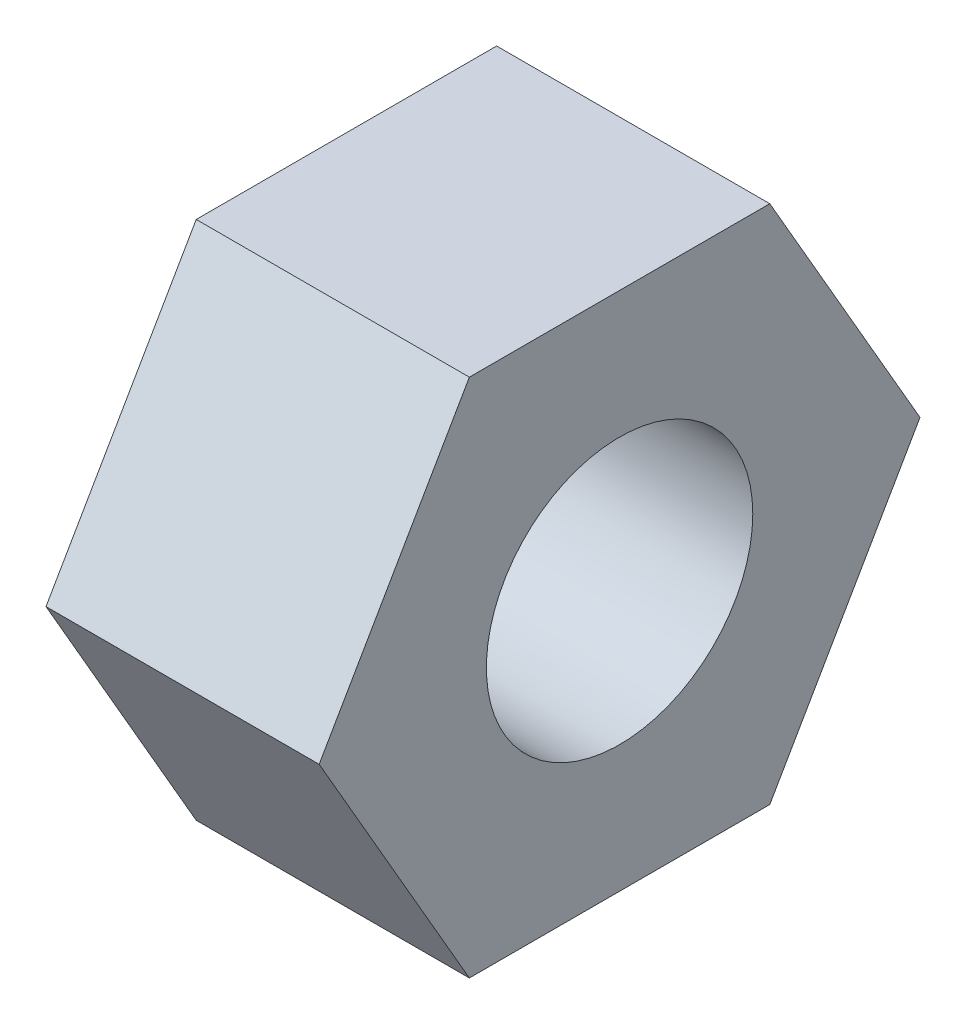
SolidWorks part; units mm, degrees
material "6061-T4 (SS)"
ref_plane "Front Plane" through (0, 0, 0) normal (0, 0, 1) x (1, 0, 0)
ref_plane "Top Plane" through (0, 0, 0) normal (0, 1, 0) x (1, 0, 0)
ref_plane "Right Plane" through (0, 0, 0) normal (1, 0, 0) x (0, 0, -1)
sketch "Sketch1" plane through (0, 0, 0) normal (1, 0, 0) x (0, 0, -1)
  line L0 (0, 0) -> (2.7496, 0) construction
  line L1 (2.7496, 0) -> (1.3748, 2.3812)
  line L2 (1.3748, 2.3812) -> (-1.3748, 2.3813)
  line L3 (-1.3748, 2.3813) -> (-2.7496, 0)
  line L4 (-2.7496, 0) -> (-1.3748, -2.3813)
  line L5 (-1.3748, -2.3813) -> (1.3748, -2.3813)
  line L6 (1.3748, -2.3813) -> (2.7496, 0)
  circle A0 centre (0, 0) radius 2.3812 construction
  point P1 (-2.0622, 1.1906)
  dimension "D1" = 4.7625
extrude "Boss-Extrude1" add sketch "Sketch1" along normal blind 2.5
sketch "Sketch2" plane through (2.5, 0, 0) normal (1, 0, 0) x (0, 0, -1)
  circle A0 centre (0, 0) radius 1.0922
  dimension "D1" = 2.1844
hole_wizard "#2 Clearance Hole1" positions "Sketch3" profile "Sketch4" hole size "#2" standard "ANSI Inch" end condition through all
sketch "Sketch3" plane through (2.5, 0, 0) normal (1, 0, 0) x (0, 0, -1)
  point P0 (0, 0)
sketch "Sketch4" plane through (2.5, 0, 0) normal (0, 1, 0) x (0, 0, -1)
  line L0 (0, 0) -> (0, 2.5)
  line L1 (0, 2.5) -> (1.2192, 2.5)
  line L2 (1.2192, 2.5) -> (1.2192, 0)
  line L5 (1.2192, 0) -> (0, 0)
  line L11 (0, -6.35) -> (0, 107.95) construction
  dimension "Thru Hole Dia." = 2.4384
  dimension "Thru Hole Depth" = 2.5
